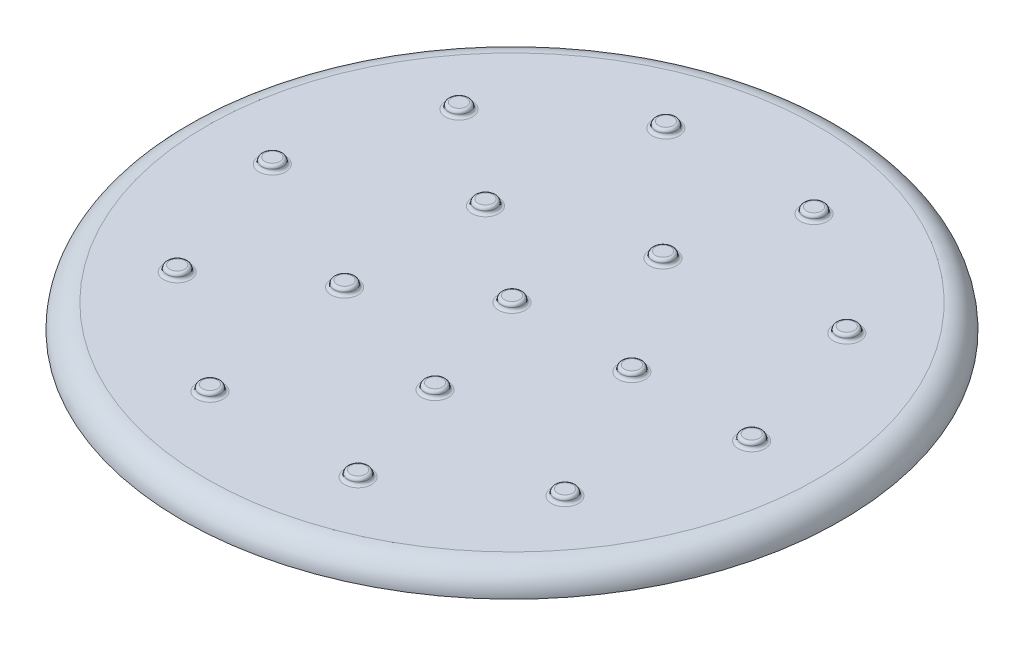
SolidWorks part; units mm, degrees
ref_plane "Front Plane" through (0, 0, 0) normal (0, 0, 1) x (1, 0, 0)
ref_plane "Top Plane" through (0, 0, 0) normal (0, 1, 0) x (1, 0, 0)
ref_plane "Right Plane" through (0, 0, 0) normal (1, 0, 0) x (0, 0, -1)
sketch "Sketch1" plane through (0, 0, 0) normal (0, 1, 0) x (1, 0, 0)
  circle A0 centre (0, 0) radius 55
  dimension "D1" = 110
extrude "Boss-Extrude1" add sketch "Sketch1" along normal blind 4
sketch "Sketch4" plane through (0, 0, 0) normal (0, 0, 1) x (1, 0, 0)
  line L0 (0, 0) -> (0, 27.2763) construction
fillet "Fillet4" radius 4 1 edges at (0, 4, 55)
sketch "Sketch5" plane through (0, 4, 0) normal (0, 1, 0) x (1, 0, 0)
  circle A0 centre (0, 0) radius 1.75
  circle A1 centre (20, 0) radius 1.75
  circle A2 centre (40, 0) radius 1.75
  circle A3 centre (6.1803, -19.0211) radius 1.75
  circle A4 centre (-16.1803, -11.7557) radius 1.75
  circle A5 centre (-16.1803, 11.7557) radius 1.75
  circle A6 centre (6.1803, 19.0211) radius 1.75
  circle A7 centre (32.3607, -23.5114) radius 1.75
  circle A8 centre (12.3607, -38.0423) radius 1.75
  circle A9 centre (-12.3607, -38.0423) radius 1.75
  circle A10 centre (-32.3607, -23.5114) radius 1.75
  circle A11 centre (-40, 0) radius 1.75
  circle A12 centre (-32.3607, 23.5114) radius 1.75
  circle A13 centre (-12.3607, 38.0423) radius 1.75
  circle A14 centre (12.3607, 38.0423) radius 1.75
  circle A15 centre (32.3607, 23.5114) radius 1.75
  point P18 (0, 0)
  point P37 (0, 0)
  dimension "D1" = 3.5
  dimension "D2" = 3
  dimension "D3" = 5
  dimension "D4" = 10
extrude "Boss-Extrude3" add sketch "Sketch5" along normal blind 1
fillet "Fillet6" radius 0.5 32 edges at (0, 4, 1.75) (0, 5, 1.75) (20, 4, 1.75) (20, 5, 1.75) (40, 4, 1.75) (40, 5, 1.75) (6.1803, 4, 20.7711) (6.1803, 5, 20.7711) (-16.1803, 4, 13.5057) (-16.1803, 5, 13.5057) (-16.1803, 4, -10.0057) (-16.1803, 5, -10.0057) (6.1803, 4, -17.2711) (6.1803, 5, -17.2711) (32.3607, 4, 25.2614) (32.3607, 5, 25.2614) (12.3607, 4, 39.7923) (12.3607, 5, 39.7923) (-12.3607, 4, 39.7923) (-12.3607, 5, 39.7923) (-32.3607, 4, 25.2614) (-32.3607, 5, 25.2614) (-40, 4, 1.75) (-40, 5, 1.75) (-32.3607, 4, -21.7614) (-32.3607, 5, -21.7614) (-12.3607, 4, -36.2923) (-12.3607, 5, -36.2923) (12.3607, 4, -36.2923) (12.3607, 5, -36.2923) (32.3607, 4, -21.7614) (32.3607, 5, -21.7614)
